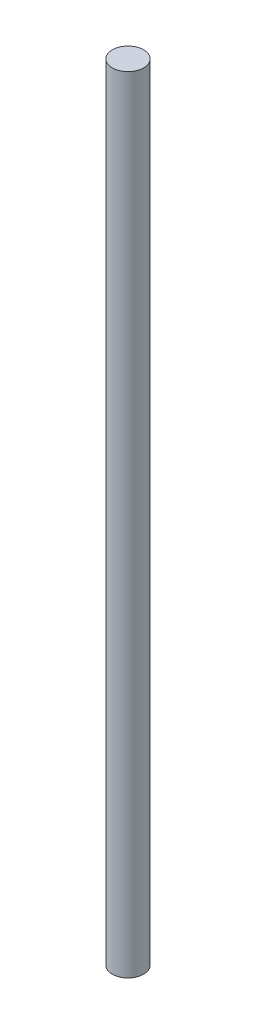
SolidWorks part; units mm, degrees
ref_plane "Front Plane" through (0, 0, 0) normal (0, 0, 1) x (1, 0, 0)
ref_plane "Top Plane" through (0, 0, 0) normal (0, 1, 0) x (1, 0, 0)
ref_plane "Right Plane" through (0, 0, 0) normal (1, 0, 0) x (0, 0, -1)
sketch "Sketch1" plane through (0, 0, 0) normal (0, 1, 0) x (1, 0, 0)
  circle A0 centre (0, 0) radius 3
  dimension "D1" = 6
extrude "Boss-Extrude1" add sketch "Sketch1" along normal blind 150
